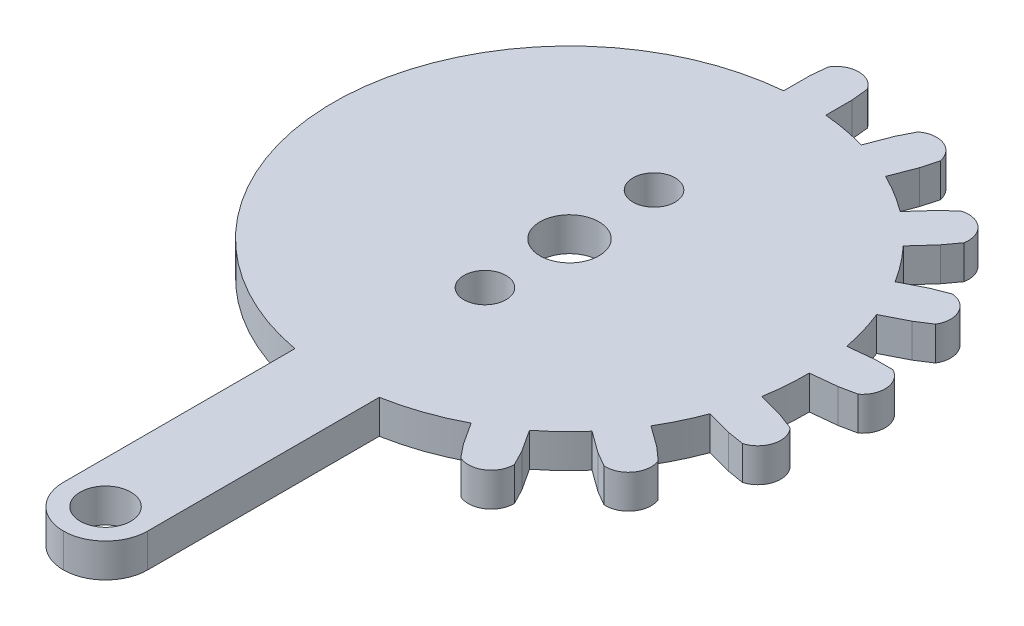
SolidWorks part; units mm, degrees
material "1023 Carbon Steel Sheet (SS)"
ref_plane "Front Plane" through (0, 0, 0) normal (0, 0, 1) x (1, 0, 0)
ref_plane "Top Plane" through (0, 0, 0) normal (0, 1, 0) x (1, 0, 0)
ref_plane "Right Plane" through (0, 0, 0) normal (1, 0, 0) x (0, 0, -1)
sketch "Sketch1" plane through (0, 0, 0) normal (0, 1, 0) x (1, 0, 0)
  line L2 (1.25, 15.5) -> (1.15, 16.5)
  line L4 (-1.15, 16.5) -> (-1.25, 15.5)
  line L8 (-1.25, 13.9441) -> (-1.25, 15.5)
  line L9 (1.25, 13.9441) -> (1.25, 15.5)
  line L12 (3.8301, 13.4659) -> (4.3877, 14.9185)
  line L15 (6.1641, 12.57) -> (6.7217, 14.0225)
  line L16 (6.7217, 14.0225) -> (6.9867, 14.992)
  line L17 (4.8395, 15.8162) -> (4.3877, 14.9185)
  line L18 (8.4015, 11.1989) -> (9.4426, 12.3552)
  line L21 (10.2593, 9.5261) -> (11.3005, 10.6823)
  line L22 (11.3005, 10.6823) -> (11.8953, 11.4924)
  line L23 (10.186, 13.0314) -> (9.4426, 12.3552)
  line L24 (11.8568, 7.4442) -> (13.2431, 8.1506)
  line L27 (12.9918, 5.2167) -> (14.3781, 5.9231)
  line L28 (14.3781, 5.9231) -> (15.2237, 6.4662)
  line L29 (14.1795, 8.5155) -> (13.2431, 8.1506)
  line L30 (13.737, 2.7007) -> (15.2844, 2.8633)
  line L33 (13.9984, 0.2144) -> (15.5457, 0.377)
  line L34 (15.5457, 0.377) -> (16.5298, 0.581)
  line L35 (16.2894, 2.8684) -> (15.2844, 2.8633)
  line L36 (13.7925, -2.4016) -> (15.2954, -2.8043)
  line L39 (13.1454, -4.8164) -> (14.6483, -5.2191)
  line L40 (14.6483, -5.2191) -> (15.6401, -5.3813)
  line L41 (16.2354, -3.1597) -> (15.2954, -2.8043)
  line L42 (12.0157, -7.1849) -> (13.2745, -8.0994)
  line L45 (10.5463, -9.2074) -> (11.805, -10.1219)
  line L46 (11.805, -10.1219) -> (12.6728, -10.6288)
  line L47 (14.0247, -8.7681) -> (13.2745, -8.0994)
  line L48 (8.6428, -11.0137) -> (9.4902, -12.3186)
  line L52 (-2.5, -13.775) -> (-2.5, -30)
  line L53 (-2.5, -30) -> (2.5, -30)
  line L54 (2.5, -13.775) -> (2.5, -30)
  line L57 (6.5462, -12.3753) -> (7.3936, -13.6802)
  line L58 (7.3936, -13.6802) -> (8.0221, -14.4644)
  line L59 (9.951, -13.2117) -> (9.4902, -12.3186)
  line L60 (0, 0) -> (1.25, 13.9441) construction
  line L61 (0, 0) -> (6.1641, 12.57) construction
  arc A0 (-1.25, 13.9441) -> (-2.5, -13.775) centre (0, 0) ccw
  arc A1 (-1.15, 16.5) -> (1.15, 16.5) centre (0, 15.795) cw
  arc A2 (4.8395, 15.8162) -> (6.9867, 14.992) centre (5.6604, 14.7459) cw
  arc A3 (10.186, 13.0314) -> (11.8953, 11.4924) centre (10.5689, 11.738) cw
  arc A4 (14.1795, 8.5155) -> (15.2237, 6.4662) centre (14.0734, 7.1708) cw
  arc A5 (16.2894, 2.8684) -> (16.5298, 0.581) centre (15.7085, 1.651) cw
  arc A6 (16.2354, -3.1597) -> (15.6401, -5.3813) centre (15.2568, -4.088) cw
  arc A7 (14.0247, -8.7681) -> (12.6728, -10.6288) centre (12.7784, -9.2841) cw
  arc A8 (9.951, -13.2117) -> (8.0221, -14.4644) centre (8.6026, -13.2468) cw
  arc A9 (2.5, -13.775) -> (6.5462, -12.3753) centre (0, 0) ccw
  arc A10 (8.4015, 11.1989) -> (6.1641, 12.57) centre (0, 0) ccw
  arc A11 (11.8568, 7.4442) -> (10.2593, 9.5261) centre (0, 0) ccw
  arc A12 (13.737, 2.7007) -> (12.9918, 5.2167) centre (0, 0) ccw
  arc A13 (13.7925, -2.4016) -> (13.9984, 0.2144) centre (0, 0) ccw
  arc A14 (12.0157, -7.1849) -> (13.1454, -4.8164) centre (0, 0) ccw
  arc A15 (3.8301, 13.4659) -> (1.25, 13.9441) centre (0, 0) ccw
  arc A16 (8.6428, -11.0137) -> (10.5463, -9.2074) centre (0, 0) ccw
  point P6 (0, 14)
  point P63 (0.0002, 0)
  point P77 (0.1697, 0.1611)
  dimension "D1" = 28
  dimension "D7" = 1.3489
  dimension "D2" = 2.5
  dimension "D3" = 1.5
  dimension "D4" = 2.3
  dimension "D5" = 1.15
  dimension "D6" = 21
  dimension "D8" = 1
  dimension "D10" = 5
  dimension "D12" = 2.5
  dimension "D14" = 8
extrude "Boss-Extrude1" add sketch "Sketch1" along normal mid plane 2 contours A0 | A0 | A0 | A0 | A0 | A0 | A0 | A1 L4 A0 L2 region at (0.7764, 0, 2.1109)
sketch "Sketch5" plane through (0, 1, 0) normal (0, 1, 0) x (1, 0, 0)
  line L0 (0, 0) -> (-0.4355, 0) construction
  circle A0 centre (0, 0) radius 1.75
  circle A1 centre (0, 5.0112) radius 1.25
  circle A2 centre (0, -5.0112) radius 1.25
  dimension "D1" = 2.5
  dimension "D2" = 3.5
  dimension "D3" = 2.5
  dimension "D4" = 5.0112
  dimension "D5" = 5.0112
extrude "Cut-Extrude3" cut sketch "Sketch5" against normal through all
fillet "Fillet1" radius 2.5 2 edges at (-2.5, 0, 30) (2.5, 0, 30)
sketch "Sketch6" plane through (0, 1, 0) normal (0, 1, 0) x (1, 0, 0)
  circle A0 centre (0, -27.5) radius 1.5
  dimension "D1" = 3
extrude "Cut-Extrude4" cut sketch "Sketch6" against normal through all
